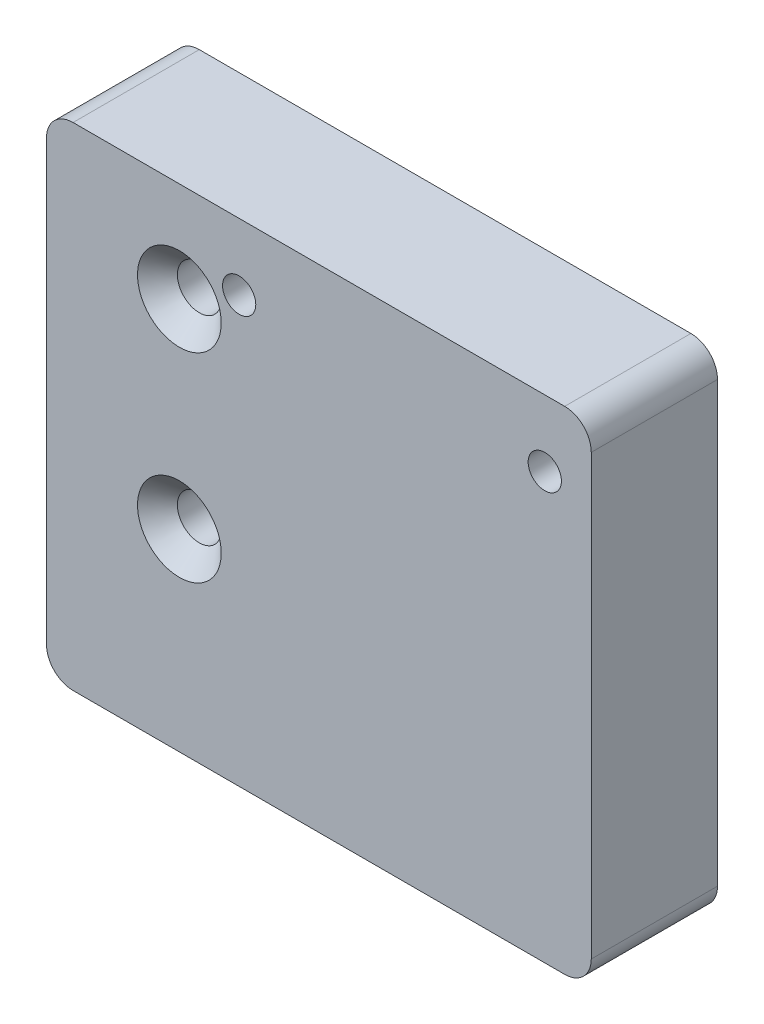
SolidWorks part; units mm, degrees
ref_plane "Front Plane" through (0, 0, 0) normal (0, 0, 1) x (1, 0, 0)
ref_plane "Top Plane" through (0, 0, 0) normal (0, 1, 0) x (1, 0, 0)
ref_plane "Right Plane" through (0, 0, 0) normal (1, 0, 0) x (0, 0, -1)
sketch "Sketch1" plane through (0, 0, 0) normal (0, 0, 1) x (1, 0, 0)
  line L1 (62, 72.839) -> (-20, 72.839)
  line L2 (62, 72.839) -> (62, 12.839)
  line L3 (62, 12.839) -> (-20, 12.839)
  line L4 (-20, 72.839) -> (-20, 12.839)
  dimension "D1" = 60
extrude "Boss-Extrude1" add sketch "Sketch1" along normal blind 19
hole_wizard "Tap Drill for M6 Tap1" positions "Sketch4" profile "Sketch3" hole size "M6" standard "ISO" end condition through all
sketch "Sketch4" plane through (0, 0, 19) normal (0, 0, 1) x (1, 0, 0)
  point P0 (9, 62.839)
  point P3 (55, 62.839)
sketch "Sketch3" plane through (9, 62.839, 19) normal (1, 0, 0) x (0, -1, 0)
  line L0 (0, 0) -> (0, 19)
  line L1 (0, 19) -> (2.5, 19)
  line L2 (2.5, 19) -> (2.5, 0)
  line L5 (2.5, 0) -> (0, 0)
  line L11 (0, -6.35) -> (0, 107.95) construction
  dimension "Thru Hole Dia." = 5
  dimension "Thru Hole Depth" = 19
hole_wizard "CSK for M6 Countersunk Flat Head Screw1" positions "Sketch5" profile "Sketch6" countersink size "M6" standard "ISO" end condition through all
sketch "Sketch5" plane through (0, 0, 19) normal (0, 0, 1) x (1, 0, 0)
  line L0 (-20, 12.839) -> (62, 12.839) construction
  point P0 (0, 27.839)
  point P2 (0, 57.839)
  dimension "D1" = 30
  dimension "D2" = 15
sketch "Sketch6" plane through (0, 27.839, 19) normal (1, 0, 0) x (0, -1, 0)
  line L0 (0, 0) -> (0, 19)
  line L1 (0, 19) -> (3.3, 19)
  line L2 (3.3, 19) -> (3.3, 3)
  line L3 (3.3, 3) -> (6.3, 0)
  line L5 (6.3, 0) -> (0, 0)
  line L6 (-3.3, 3) -> (-6.3, 0) construction
  line L11 (0, -6.35) -> (0, 107.95) construction
  dimension "Thru Hole Dia." = 6.6
  dimension "Thru Hole Depth" = 19
  dimension "Near C'Sink Dia." = 12.6
  dimension "Near C'Sink Angle" = 90
sketch "Sketch7" plane through (0, 0, 19) normal (0, 0, 1) x (1, 0, 0)
  line L0 (62, 12.839) -> (62, 72.839) construction
  line L1 (62, 12.8434) -> (-20, 12.8434)
  line L2 (62, 12.8434) -> (62, -1.211)
  line L3 (62, -1.211) -> (-20, -1.211)
  line L4 (-20, 12.8434) -> (-20, -1.211)
extrude "Boss-Extrude2" add sketch "Sketch7" against normal up to surface (19 mm away) up to face at (3.3, 27.839, 0)
hole_wizard "Tap Drill for M5 Tap1" positions "Sketch8" profile "Sketch9" hole size "M5" standard "ISO"
sketch "Sketch8" plane through (0, -1.211, 0) normal (0, -1, 0) x (-1, 0, 0)
  point P0 (-42, -9.5)
sketch "Sketch9" plane through (42, -1.211, 9.5) normal (1, 0, 0) x (0, 0, -1)
  line L0 (0, 0) -> (0, 31.2618)
  line L1 (0, 31.2618) -> (2.1, 30)
  line L2 (2.1, 30) -> (2.1, 0)
  line L5 (2.1, 0) -> (0, 0)
  line L10 (0, 31.2618) -> (-2.1, 30) construction
  line L11 (0, -6.35) -> (0, 107.95) construction
  dimension "Hole Dia." = 4.2
  dimension "Hole Depth" = 30
  dimension "Drill Angle" = 118
fillet "Fillet1" radius 4 4 edges at (-20, -1.211, 9.5) (62, 72.839, 9.5) (62, -1.211, 9.5) (-20, 72.839, 9.5)
